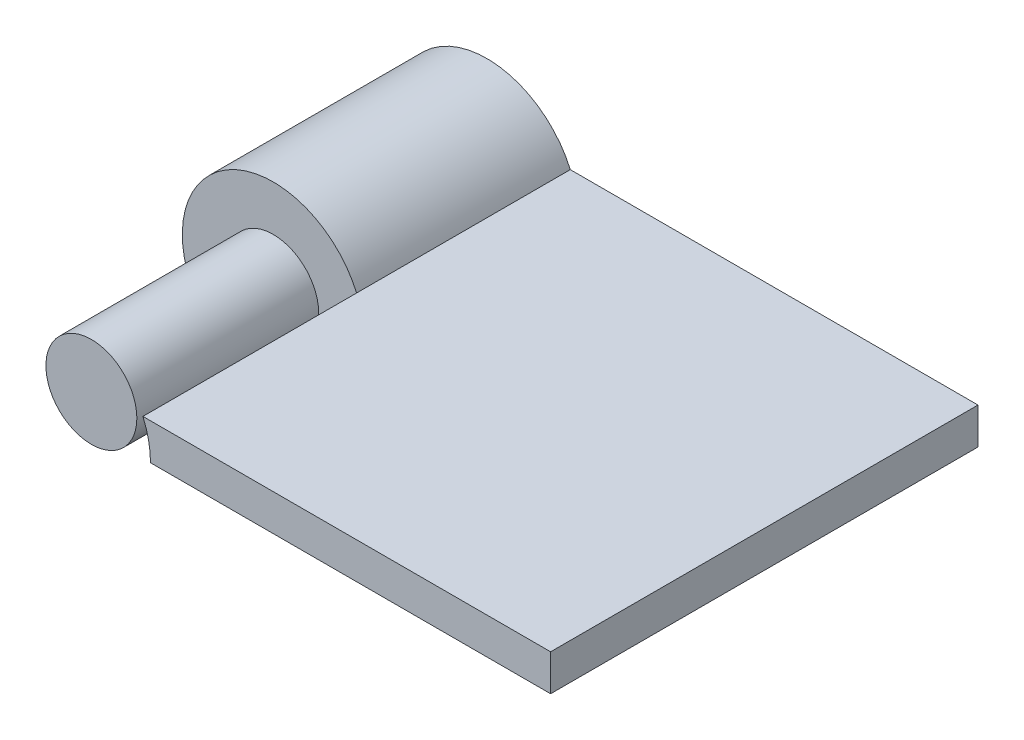
SolidWorks part; units mm, degrees
ref_plane "Front Plane" through (0, 0, 0) normal (0, 0, 1) x (1, 0, 0)
ref_plane "Top Plane" through (0, 0, 0) normal (0, 1, 0) x (1, 0, 0)
ref_plane "Right Plane" through (0, 0, 0) normal (1, 0, 0) x (0, 0, -1)
sketch "Sketch1" plane through (0, 0, 0) normal (0, 0, 1) x (1, 0, 0)
  line L0 (0, 0) -> (37.505, 0) construction
  line L2 (0, 0) -> (54, 0)
  line L3 (0, 0) -> (0, 4)
  line L4 (0, 4) -> (54, 4)
  line L5 (54, 0) -> (54, 4)
  circle A0 centre (0, 0) radius 10
  circle A1 centre (0, 0) radius 5
  dimension "D1" = 20
  dimension "D2" = 10
  dimension "D3" = 4
  dimension "D4" = 54
extrude "Boss-Extrude1" add sketch "Sketch1" along normal blind 23.5 contours A0
extrude "Boss-Extrude2" add sketch "Sketch1<3>" along normal blind 20 from surface contours A1 starting at face at (10, 0, 23.5)
sketch "Sketch1<3>" plane through (0, 0, 0) normal (0, 0, 1) x (1, 0, 0) same geometry as "Sketch1"
extrude "Boss-Extrude3" add sketch "Sketch1<4>" along normal blind 47 contours A0 L2 L5 L4 region at (31.8626, 2.0062, 0)
sketch "Sketch1<4>" plane through (0, 0, 0) normal (0, 0, 1) x (1, 0, 0) same geometry as "Sketch1"
